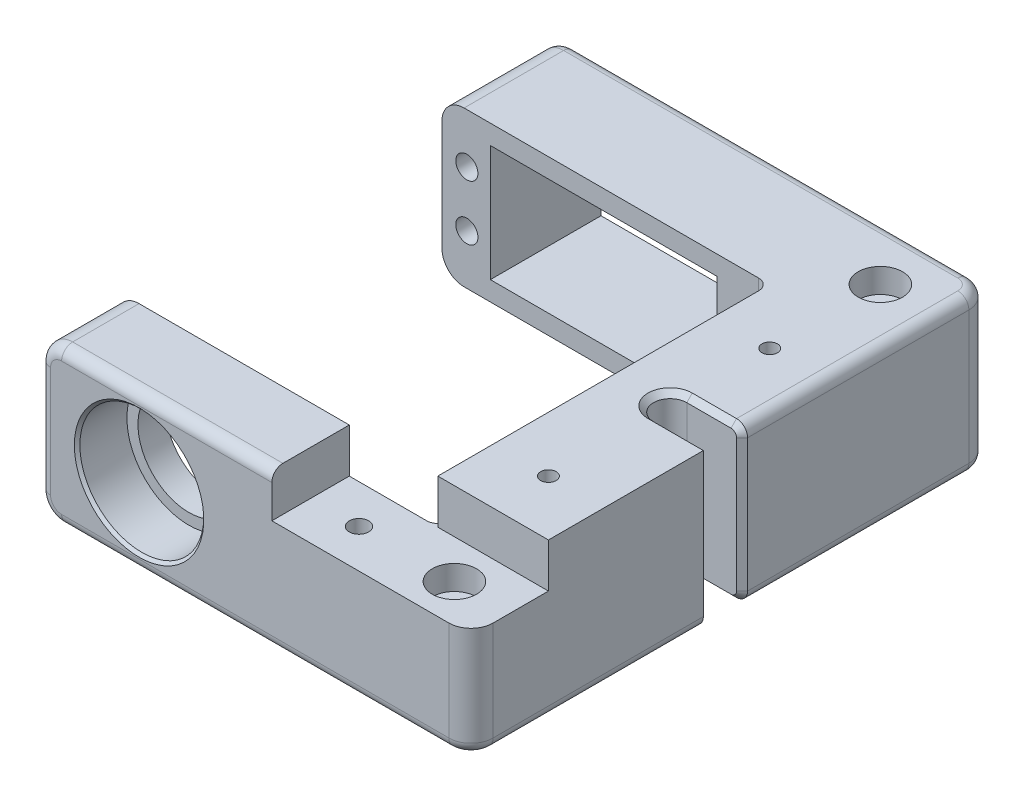
SolidWorks part; units mm, degrees
ref_plane "Top Plane" through (0, 0, 0) normal (0, 0, 1) x (1, 0, 0)
ref_plane "Right Plane" through (0, 0, 0) normal (0, 1, 0) x (1, 0, 0)
ref_plane "Front Plane" through (0, 0, 0) normal (1, 0, 0) x (0, 0, -1)
sketch "Sketch1" plane through (0, 0, 0) normal (0, 0, 1) x (1, 0, 0)
  line L0 (-10, 0) -> (30, 0) construction
  line L1 (-10, 10) -> (30, 10) construction
  line L2 (-10, 10) -> (-10, -10) construction
  line L3 (-10, -10) -> (30, -10) construction
  line L4 (30, 10) -> (30, -10) construction
  line L5 (-10, 10) -> (-17.25, 10) construction
  line L6 (-17.25, 10) -> (-17.25, -10) construction
  line L7 (-17.25, -10) -> (-10, -10) construction
  line L8 (10, 10) -> (10, -10) construction
  line L9 (37.25, -10) -> (30, -10) construction
  line L10 (37.25, 10) -> (37.25, -10) construction
  line L11 (30, 10) -> (37.25, 10) construction
  line L12 (40, 14) -> (40, -14) construction
  line L13 (-19.25, 14) -> (60, 14)
  line L14 (-19.25, 14) -> (-19.25, -14)
  line L15 (-19.25, -14) -> (60, -14)
  line L16 (60, 14) -> (60, -14)
  circle A0 centre (0, 0) radius 11 construction
  circle A1 centre (0, 0) radius 4 construction
  circle A2 centre (-14.75, 5) radius 2 construction
  circle A3 centre (-14.75, -5) radius 2 construction
  circle A4 centre (34.75, -5) radius 2 construction
  circle A5 centre (34.75, 5) radius 2 construction
  dimension "D1" = 22
  dimension "D2" = 8
  dimension "D12" = 4
  dimension "D3" = 40
  dimension "D4" = 20
  dimension "D5" = 54.5
  dimension "D6" = 37.25
  dimension "D7" = 20
  dimension "D8" = 40
  dimension "D9" = 14
  dimension "D10" = 14
  dimension "D11" = 2
  dimension "D13" = 10
  dimension "D14" = 49.5
extrude "Boss-Extrude1" add sketch "Sketch1" along normal blind 20
sketch "Sketch2" plane through (0, 0, 20) normal (0, 0, 1) x (1, 0, 0)
  line L1 (40, 14) -> (60, 14)
  line L2 (40, 14) -> (40, -14)
  line L3 (40, -14) -> (60, -14)
  line L4 (60, 14) -> (60, -14)
extrude "Boss-Extrude2" add sketch "Sketch2" along normal blind 60
sketch "Sketch3" plane through (0, 0, 80) normal (0, 0, 1) x (1, 0, 0)
  line L0 (-19.25, -14) -> (60, -14) construction
  line L1 (60, 14) -> (-18, 14)
  line L2 (60, 14) -> (60, -14)
  line L3 (60, -14) -> (-18, -14)
  line L4 (-18, 14) -> (-18, -14)
  dimension "D1" = 18
extrude "Boss-Extrude3" add sketch "Sketch3" along normal blind 14
sketch "Sketch4" plane through (0, 0, 20) normal (0, 0, 1) x (1, 0, 0)
  line L8 (-10.5, -10.5) -> (30.5, -10.5)
  line L9 (30.5, -10.5) -> (30.5, 10.5)
  line L10 (30.5, 10.5) -> (-10.5, 10.5)
  line L11 (-10.5, 10.5) -> (-10.5, -10.5)
  line L12 (-10.5, -10.5) -> (30.5, -10.5)
  line L13 (30.5, -10.5) -> (30.5, 10.5)
  line L14 (30.5, 10.5) -> (-10.5, 10.5)
  line L15 (-10.5, 10.5) -> (-10.5, -10.5)
  dimension "D1" = 0.5
extrude "Cut-Extrude1" cut sketch "Sketch4" against normal through all
sketch "Sketch5" plane through (0, 0, 20) normal (0, 0, 1) x (1, 0, 0)
  circle A0 centre (34.75, -5) radius 2 construction
  circle A1 centre (34.75, 5) radius 2 construction
  circle A2 centre (-14.75, -5) radius 2 construction
  circle A3 centre (-14.75, 5) radius 2 construction
  circle A4 centre (34.75, -5) radius 2
  circle A5 centre (34.75, 5) radius 2
  circle A6 centre (-14.75, -5) radius 2
  circle A7 centre (-14.75, 5) radius 2
extrude "Cut-Extrude2" cut sketch "Sketch5" against normal through all
sketch "Sketch6" plane through (0, 0, 0) normal (0, 0, -1) x (-1, 0, 0)
  line L0 (-10, 10.5) -> (-10, -10.5) construction
  line L1 (-34.75, 8.4641) -> (-37.75, 6.7321)
  line L2 (-37.75, 6.7321) -> (-37.75, 3.2679)
  line L3 (-37.75, 3.2679) -> (-34.75, 1.5359)
  line L4 (-34.75, 1.5359) -> (-31.75, 3.2679)
  line L5 (-31.75, 3.2679) -> (-31.75, 6.7321)
  line L6 (-31.75, 6.7321) -> (-34.75, 8.4641)
  line L7 (-34.75, -1.5359) -> (-37.75, -3.2679)
  line L8 (-37.75, -3.2679) -> (-37.75, -6.7321)
  line L9 (-37.75, -6.7321) -> (-34.75, -8.4641)
  line L10 (-34.75, -8.4641) -> (-31.75, -6.7321)
  line L11 (-31.75, -6.7321) -> (-31.75, -3.2679)
  line L12 (-31.75, -3.2679) -> (-34.75, -1.5359)
  line L13 (-30.5, 10.5) -> (10.5, 10.5) construction
  line L14 (10.5, -10.5) -> (-30.5, -10.5) construction
  line L15 (11.75, -3.2679) -> (14.75, -1.5359)
  line L16 (11.75, -6.7321) -> (11.75, -3.2679)
  line L17 (14.75, -8.4641) -> (11.75, -6.7321)
  line L18 (17.75, -6.7321) -> (14.75, -8.4641)
  line L19 (17.75, -3.2679) -> (17.75, -6.7321)
  line L20 (14.75, -1.5359) -> (17.75, -3.2679)
  line L21 (11.75, 6.7321) -> (14.75, 8.4641)
  line L22 (11.75, 3.2679) -> (11.75, 6.7321)
  line L23 (14.75, 1.5359) -> (11.75, 3.2679)
  line L24 (17.75, 3.2679) -> (14.75, 1.5359)
  line L25 (17.75, 6.7321) -> (17.75, 3.2679)
  line L26 (14.75, 8.4641) -> (17.75, 6.7321)
  circle A0 centre (-34.75, 5) radius 3 construction
  circle A1 centre (-34.75, -5) radius 3 construction
  circle A2 centre (14.75, -5) radius 3 construction
  circle A3 centre (14.75, 5) radius 3 construction
  dimension "D1" = 6
extrude "Cut-Extrude3" cut sketch "Sketch6" against normal offset from surface (14 mm away) 6 up to face at (36.75, 5, 20)
sketch "Sketch7" plane through (0, 0, 94) normal (0, 0, 1) x (1, 0, 0)
  circle A2 centre (0, 0) radius 11.2
  circle A3 centre (0, 0) radius 11.2
  dimension "D1" = 0.2
extrude "Cut-Extrude4" cut sketch "Sketch7" against normal blind 9
sketch "Sketch8" plane through (0, 0, 85) normal (0, 0, 1) x (1, 0, 0)
  circle A0 centre (0, 0) radius 9.2
  circle A1 centre (0, 0) radius 11.2 construction
  dimension "D1" = 2
extrude "Cut-Extrude5" cut sketch "Sketch8" against normal up to next
sketch "Sketch12" plane through (0, 14, 0) normal (0, 1, 0) x (1, 0, 0)
  line L0 (60, 0) -> (-19.25, 0) construction
  line L1 (60, -94) -> (60, 0) construction
  line L3 (35.6842, -80) -> (35.6842, -94) construction
  line L4 (40, -80) -> (-18, -80) construction
  line L5 (60, -94) -> (-18, -94) construction
  line L6 (35.6842, -87) -> (50, -87) construction
  circle A0 centre (50, -10) radius 2 construction
  circle A1 centre (50, -10) radius 3.75 construction
  circle A2 centre (50, -87) radius 2 construction
  circle A3 centre (50, -87) radius 3.75 construction
  dimension "D1" = 4
  dimension "D2" = 7.5
  dimension "D3" = 10
  dimension "D4" = 10
  dimension "D6" = 10
sketch "Sketch15" plane through (0, 14, 0) normal (0, 1, 0) x (1, 0, 0)
  line L0 (32.75, -87) -> (50, -87) construction
  circle A0 centre (32.75, -87) radius 1.75
  dimension "D1" = 17.25
  dimension "D2" = 3.5
extrude "Cut-Extrude6" cut sketch "Sketch15" against normal through all
sketch "Sketch16" plane through (0, -14, 0) normal (0, -1, 0) x (1, 0, 0)
  line L1 (31.0179, 90) -> (29.2859, 87)
  line L2 (29.2859, 87) -> (31.0179, 84)
  line L3 (31.0179, 84) -> (34.4821, 84)
  line L4 (34.4821, 84) -> (36.2141, 87)
  line L5 (36.2141, 87) -> (34.4821, 90)
  line L6 (34.4821, 90) -> (31.0179, 90)
  circle A0 centre (32.75, 87) radius 3 construction
  dimension "D1" = 6
extrude "Cut-Extrude7" cut sketch "Sketch16" against normal blind 5
sketch "Sketch17" plane through (0, 14, 0) normal (0, 1, 0) x (1, 0, 0)
  line L0 (50, -10) -> (50, -87) construction
  line L1 (50, -45) -> (60, -45)
  line L2 (60, -94) -> (60, 0) construction
  line L3 (50, -51) -> (60, -51)
  line L4 (60, -45) -> (60, -51)
  arc A0 (50, -45) -> (50, -51) centre (50, -48) ccw
  dimension "D1" = 6
  dimension "D2" = 38
extrude "Cut-Extrude8" cut sketch "Sketch17" against normal through all
sketch "Sketch18" plane through (0, 14, 0) normal (0, 1, 0) x (1, 0, 0)
  line L0 (40, -80) -> (-18, -80) construction
  line L1 (24, -80) -> (60, -80)
  line L2 (24, -80) -> (24, -94)
  line L3 (24, -94) -> (60, -94)
  line L4 (60, -80) -> (60, -94)
  dimension "D1" = 36
extrude "Cut-Extrude9" cut sketch "Sketch18" against normal blind 8
hole_wizard "CBORE for M4 Hex Socket Head Cap Screw1" positions "Sketch13" profile "Sketch14" counterbore size "M4" standard "ISO" end condition through all
sketch "Sketch13" plane through (0, 14, 0) normal (0, 1, 0) x (1, 0, 0)
  point P2 (50, -10)
  point P11 (0, 0)
sketch "Sketch14" plane through (50, 14, 10) normal (1, 0, 0) x (0, 0, 1)
  line L0 (0, 0) -> (0, 28)
  line L1 (0, 28) -> (2.15, 28)
  line L3 (2.15, 28) -> (2.15, 4.4)
  line L4 (2.15, 4.4) -> (4, 4.4)
  line L5 (4, 4.4) -> (4, 0)
  line L7 (4, 0) -> (0, 0)
  line L11 (0, -6.35) -> (0, 107.95) construction
  dimension "Thru Hole Dia." = 4.3
  dimension "Thru Hole Depth" = 28
  dimension "C'Bore Dia." = 8
  dimension "C'Bore Depth" = 4.4
hole_wizard "CBORE for M4 Hex Socket Head Cap Screw2" positions "Sketch19" profile "Sketch20" counterbore size "M4" standard "ISO" end condition through all
sketch "Sketch19" plane through (0, 6, 0) normal (0, 1, 0) x (1, 0, 0)
  point P0 (50, -87)
sketch "Sketch20" plane through (50, 6, 87) normal (1, 0, 0) x (0, 0, 1)
  line L0 (0, 0) -> (0, 20)
  line L1 (0, 20) -> (2.15, 20)
  line L3 (2.15, 20) -> (2.15, 4.4)
  line L4 (2.15, 4.4) -> (4, 4.4)
  line L5 (4, 4.4) -> (4, 0)
  line L7 (4, 0) -> (0, 0)
  line L11 (0, -6.35) -> (0, 107.95) construction
  dimension "Thru Hole Dia." = 4.3
  dimension "Thru Hole Depth" = 20
  dimension "C'Bore Dia." = 8
  dimension "C'Bore Depth" = 4.4
sketch "Sketch22" plane through (0, 14, 0) normal (0, 1, 0) x (1, 0, 0)
  line L0 (40, -50) -> (60, -50) construction
  line L1 (40, -80) -> (40, -20) construction
  line L2 (60, -45) -> (60, 0) construction
  line L3 (50, -30) -> (50, -70) construction
  circle A0 centre (50, -30) radius 1.4
  circle A1 centre (50, -70) radius 1.4
  point P10 (50, -50)
  point P11 (0, 0)
  point P12 (0, 0)
  point P13 (50, -27.7298)
  dimension "D1" = 40
  dimension "D2" = 2.8
extrude "Cut-Extrude10" cut sketch "Sketch22" against normal through all
fillet "Fillet6" radius 0.5 7 edges at (32.75, -9, 85.25) (30.1519, -9, 85.5) (32.75, -9, 84) (35.3481, -9, 85.5) (35.3481, -9, 88.5) (32.75, -9, 90) (30.1519, -9, 88.5)
fillet "Fillet1" radius 4 4 edges at (-18, -14, 87) (-18, 14, 87) (-19.25, -14, 10) (-19.25, 14, 10)
fillet "Fillet3" radius 4 2 edges at (60, 0, 0) (60, -4, 94)
fillet "Fillet4" radius 2 2 edges at (40, 0, 20) (40, -4, 80)
fillet "Fillet5" radius 2 2 edges at (60, 14, 24.5) (60, -14, 70.5)
chamfer "Chamfer1" distance 0.5 angle 45 1 edges at (11.2, 0, 94)
chamfer "Chamfer2" distance 1 angle 45 8 edges at (47, 14, 48) (47, -14, 48) (54, -14, 45) (54, -14, 51) (59.4142, -13.4142, 51) (60, 1, 51) (59.4142, -13.4142, 45) (60, 0, 45)
